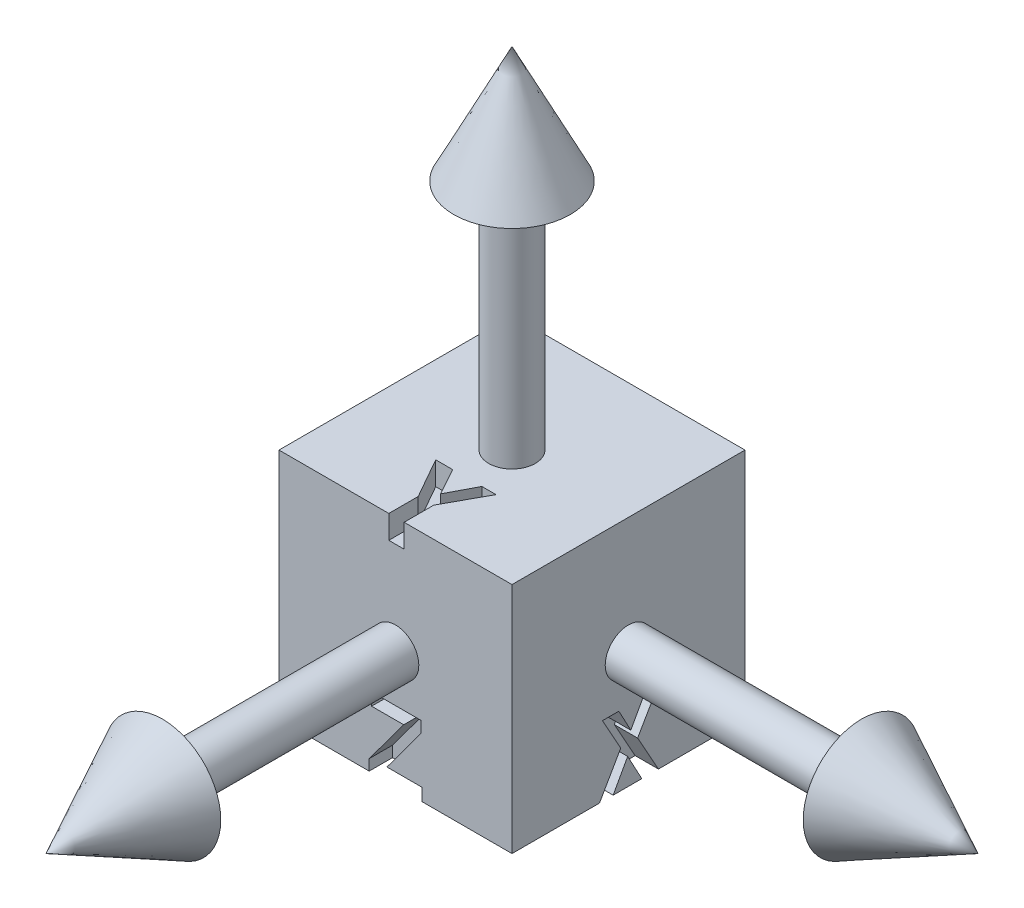
SolidWorks part; units mm, degrees
ref_plane "Front Plane" through (0, 0, 0) normal (0, 0, 1) x (1, 0, 0)
ref_plane "Top Plane" through (0, 0, 0) normal (0, 1, 0) x (1, 0, 0)
ref_plane "Right Plane" through (0, 0, 0) normal (1, 0, 0) x (0, 0, -1)
sketch "Sketch4" plane through (0, 0, 0) normal (0, 0, 1) x (1, 0, 0)
  line L0 (0, 37.5) -> (0, 0) construction
  line L1 (-5, 75) -> (5, 75)
  line L2 (-5, 75) -> (-5, 0)
  line L3 (-5, 0) -> (5, 0)
  line L4 (5, 75) -> (5, 0)
  line L5 (-5, 75) -> (5, 0) construction
  line L6 (-5, 0) -> (5, 75) construction
  line L7 (-12.5, 75) -> (12.5, 75)
  line L8 (12.5, 75) -> (0, 100)
  line L9 (0, 100) -> (-12.5, 75)
  line L10 (0, 100) -> (0, 0)
  point P0 (0, 37.5)
  point P8 (11.5369, 73.4192)
  point P12 (0, 0)
  point P13 (-11.9498, 74.9206)
  point P14 (1.7776, 100)
  dimension "D1" = 10
  dimension "D2" = 100
  dimension "D3" = 25
  dimension "D4" = 25
revolve "Revolve1" add sketch "Sketch4" angle 360 about L10 region at (4.1667, 83.3333, 0) region at (2.5, 37.5, 0)
sketch "Sketch5" plane through (0, 0, 0) normal (0, 0, 1) x (1, 0, 0)
  line L0 (0, 10) -> (0, -10)
  arc A0 (0, -10) -> (0, 10) centre (0, 0) ccw
  dimension "D1" = 20
revolve "Revolve2" add sketch "Sketch5" angle 360 about L0
move or copy body "Body-Move/Copy1" bodies to move or copy 102 copy yes number of copies 1 rotation origin (0, 0, 0) rotation axis (0, 0, -1) rotation angle 90
move or copy body "Body-Move/Copy2" bodies to move or copy 102 copy yes number of copies 1 rotation origin (0, 0, 0) rotation axis (1, 0, 0) rotation angle 90
sketch "Sketch6" plane through (0, 0, 0) normal (0, 1, 0) x (1, 0, 0)
  line L1 (-25, -25) -> (25, -25)
  line L2 (-25, -25) -> (-25, 25)
  line L3 (-25, 25) -> (25, 25)
  line L4 (25, -25) -> (25, 25)
  line L5 (-25, -25) -> (25, 25) construction
  line L6 (-25, 25) -> (25, -25) construction
  point P0 (0, 0)
  dimension "D1" = 50
  dimension "D2" = 50
extrude "Boss-Extrude2" add sketch "Sketch6" along normal blind 25 and the other way blind 25 separate body
sketch "Sketch7" plane through (0, 25, 0) normal (0, 1, 0) x (1, 0, 0)
  text T0 "Y" font "Franklin Gothic Medium" height 15
extrude "Cut-Extrude1" cut sketch "Sketch7" against normal blind 5
sketch "Sketch8" plane through (25, 0, 0) normal (1, 0, 0) x (0, 0, -1)
  text T0 "X" font "Franklin Gothic Medium" height 15
extrude "Cut-Extrude2" cut sketch "Sketch8" against normal blind 5
sketch "Sketch9" plane through (0, 0, 25) normal (0, 0, 1) x (1, 0, 0)
  text T0 "Z" font "Franklin Gothic Medium" height 15
extrude "Cut-Extrude3" cut sketch "Sketch9" against normal blind 5
